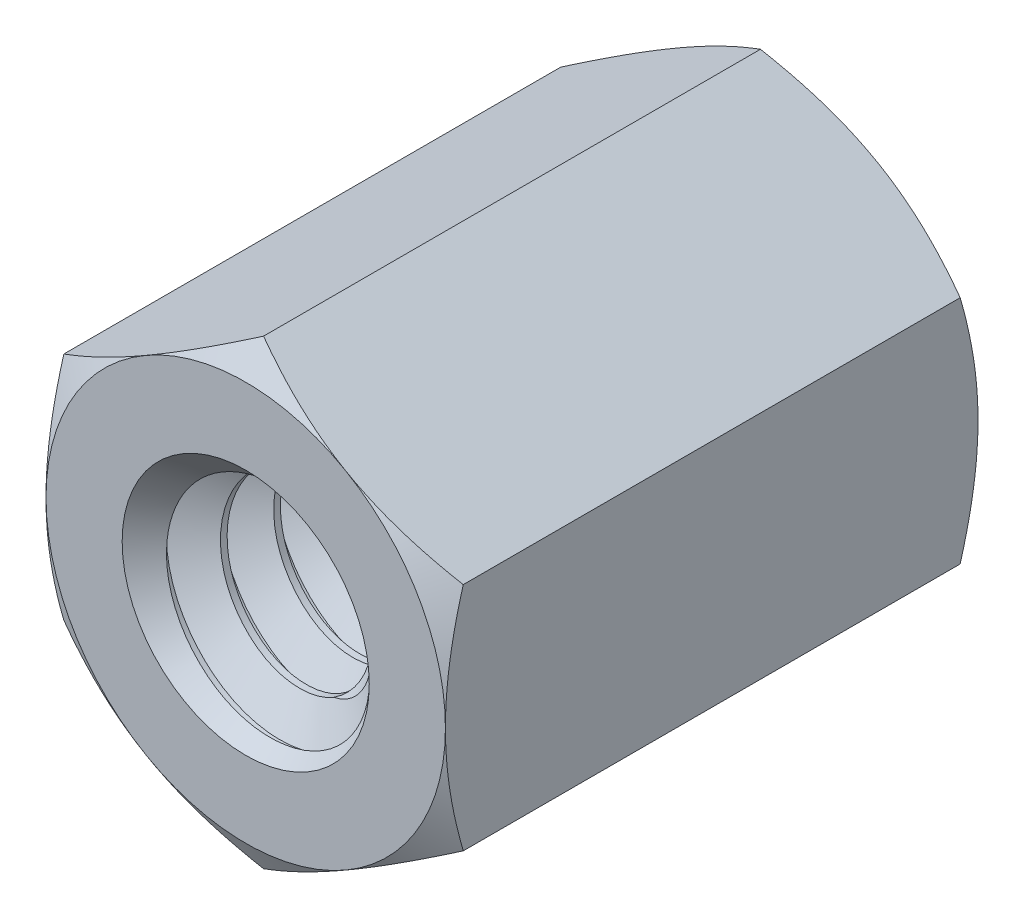
SolidWorks part; units mm, degrees
ref_plane "Front Plane" through (0, 0, 0) normal (0, 0, 1) x (1, 0, 0)
ref_plane "Top Plane" through (0, 0, 0) normal (0, 1, 0) x (1, 0, 0)
ref_plane "Right Plane" through (0, 0, 0) normal (1, 0, 0) x (0, 0, -1)
sketch "Sketch3" plane through (0, 0, 0) normal (1, 0, 0) x (0, 0, -1)
  line L0 (-3.175, 0) -> (3.175, 0) construction
  line L1 (0, 2.3813) -> (0, -2.3813) construction
  line L2 (-3.175, 1.4224) -> (-3.175, -1.4224) construction
  point P2 (-1.5875, 0)
  point P3 (1.5875, 0)
  dimension "D1" = 4.7625
  dimension "Length" = 6.35
  dimension "Min Thread Length" = 4.7625
  dimension "Thread Dia" = 2.8448
  dimension "Hex" = 4.7625
sketch "Sketch1" plane through (0, 0, 0) normal (0, 0, 1) x (1, 0, 0)
  line L1 (0, 2.7496) -> (-2.3813, 1.3748)
  line L2 (-2.3813, 1.3748) -> (-2.3813, -1.3748)
  line L3 (-2.3813, -1.3748) -> (0, -2.7496)
  line L4 (0, -2.7496) -> (2.3813, -1.3748)
  line L5 (2.3813, -1.3748) -> (2.3813, 1.3748)
  line L6 (2.3813, 1.3748) -> (0, 2.7496)
  circle A0 centre (0, 0) radius 2.3813 construction
  circle A1 centre (0, 0) radius 1.4224
extrude "Extrude1" add sketch "Sketch1" along normal up to vertex (3.175 mm away) and the other way up to vertex (3.175 mm away) up to point (0, 0, 3.175) other way up to point (0, 0, -3.175)
sketch "Sketch11" plane through (0, 0, -3.175) normal (0, 0, -1) x (-1, 0, 0)
  circle A0 centre (0, 0) radius 1.4224 construction
  circle A1 centre (0, 0) radius 1.4224
curve "Helix/Spiral1" pitch 0.635 height 6.985 radius 1.4224 centre (0, 0, -3.175) axis (0, 0, 1) start towards (0, 1, 0) parameters "Pitch"=0.635
sketch "Sketch12" plane through (0, 0, 0) normal (1, 0, 0) x (0, 0, -1)
  line L0 (3.7306, 1.4224) -> (3.175, 1.4224)
  line L1 (3.7306, 1.4224) -> (3.4925, 1.01)
  line L2 (3.4925, 1.01) -> (3.4131, 1.01)
  line L3 (3.4131, 1.01) -> (3.175, 1.4224)
  line L4 (3.4528, 1.01) -> (3.4528, 1.4224) construction
  line L5 (3.6116, 1.2162) -> (3.2941, 1.2162) construction
  dimension "D1" = 0.0794
  dimension "D2" = 0.3175
  dimension "D3" = 60
sweep "Sweep1" add profiles "Sketch12" path "Helix/Spiral1"
sketch "Sketch6" plane through (0, 0, -3.175) normal (0, 0, -1) x (-1, 0, 0)
  line L6 (0, 2.7496) -> (-2.3813, 1.3748)
  line L7 (-2.3813, 1.3748) -> (-2.3813, -1.3748)
  line L8 (-2.3813, -1.3748) -> (0, -2.7496)
  line L9 (0, -2.7496) -> (2.3813, -1.3748)
  line L10 (2.3813, -1.3748) -> (2.3813, 1.3748)
  line L11 (2.3813, 1.3748) -> (0, 2.7496)
  line L12 (0, 2.7496) -> (-2.3813, 1.3748)
  line L13 (-2.3813, 1.3748) -> (-2.3813, -1.3748)
  line L14 (-2.3813, -1.3748) -> (0, -2.7496)
  line L15 (0, -2.7496) -> (2.3813, -1.3748)
  line L16 (2.3813, -1.3748) -> (2.3813, 1.3748)
  line L17 (2.3813, 1.3748) -> (0, 2.7496)
  dimension "D1" = 0
extrude "Extrude2" cut sketch "Sketch6" along normal through all
sketch "Sketch7" plane through (0, 0, -3.175) normal (0, 0, -1) x (-1, 0, 0)
  circle A2 centre (0, 0) radius 1.4732
  circle A3 centre (0, 0) radius 1.4732
  dimension "D1" = 0.0508
extrude "Extrude3" cut sketch "Sketch7" against normal through all draft 43
sketch "Sketch8" plane through (0, 0, -3.175) normal (0, 0, -1) x (-1, 0, 0)
  circle A0 centre (0, 0) radius 2.3813 construction
  circle A1 centre (0, 0) radius 2.3813
extrude "Extrude4" cut sketch "Sketch8" against normal through all draft 60 flip side to cut
mirror "Mirror1" about plane through (0, 0, 0) normal (0, 0, 1) of "Extrude2", "Extrude3", "Extrude4"
sketch "Sketch9" [suppressed] plane through (0, 0, 0) normal (1, 0, 0) x (0, 0, -1)
  line L1 (-1.5875, 0.8128) -> (1.5875, 0.8128)
  line L2 (-1.5875, 0.8128) -> (-1.5875, 0)
  line L3 (-1.5875, 0) -> (1.5875, 0)
  line L4 (1.5875, 0.8128) -> (1.5875, 0)
  line L7 (-6.35, 0) -> (6.35, 0) construction
revolve "Revolve" [suppressed] add sketch "Sketch9" angle 360 about L0
sketch "Sketch10" [suppressed] plane through (0, 0, 0) normal (1, 0, 0) x (0, 0, -1)
  line L0 (6.35, 0.762) -> (1.5875, 0.762)
  line L1 (-6.35, 0.762) -> (-1.5875, 0.762)
  line L2 (1.5875, 0.762) -> (1.5875, -0.762)
  line L3 (-6.35, -0.8128) -> (-1.5875, -0.8128)
  line L4 (-1.5875, 0.762) -> (-1.5875, -0.8128)
  line L5 (1.5875, -0.762) -> (6.35, -0.762)
equation "\"D1@Sketch3\" = \"Min Thread Length@Sketch3\""
equation "\"D3@Helix/Spiral1\" = \"Length@Sketch3\"+\"Pitch@Helix/Spiral1\""
equation "\"D1@Sketch12\" = \"Pitch@Helix/Spiral1\"*.125"
equation "\"D2@Sketch12\" = \"Pitch@Helix/Spiral1\"*.5"
